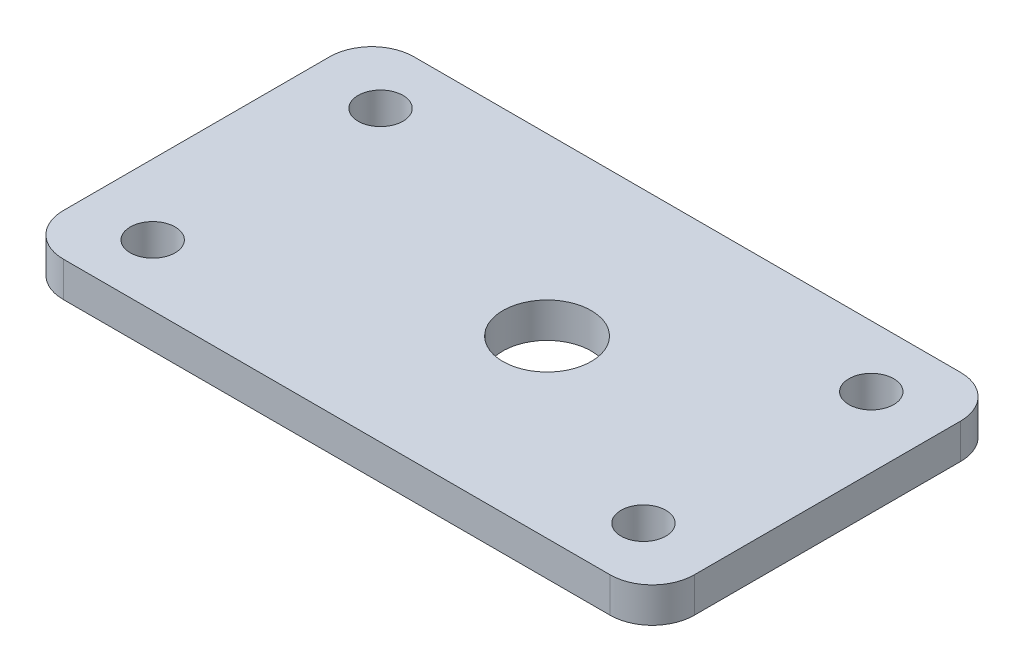
SolidWorks part; units mm, degrees
ref_plane "Front Plane" through (0, 0, 0) normal (0, 0, 1) x (1, 0, 0)
ref_plane "Top Plane" through (0, 0, 0) normal (0, 1, 0) x (1, 0, 0)
ref_plane "Right Plane" through (0, 0, 0) normal (1, 0, 0) x (0, 0, -1)
sketch "Sketch1" plane through (0, 0, 0) normal (0, 1, 0) x (1, 0, 0)
  line L0 (0, 0) -> (3.175, 0) construction
  line L1 (28.575, -15.875) -> (-28.575, -15.875)
  line L2 (28.575, -15.875) -> (28.575, 15.875)
  line L3 (28.575, 15.875) -> (-28.575, 15.875)
  line L4 (-28.575, -15.875) -> (-28.575, 15.875)
  line L5 (28.575, -15.875) -> (-28.575, 15.875) construction
  line L6 (28.575, 15.875) -> (-28.575, -15.875) construction
  circle A2 centre (3.175, 0) radius 4
  point P0 (0, 0)
  point P9 (-6.9555, 0)
  dimension "D3" = 8
  dimension "D4" = 31.75
  dimension "D1" = 57.15
  dimension "D2" = 31.75
extrude "Boss-Extrude1" add sketch "Sketch1" along normal blind 3.175 contours L3 L4 L1 L2 | A2
fillet "Fillet1" radius 3.81 4 edges at (28.575, 1.5875, -15.875) (28.575, 1.5875, 15.875) (-28.575, 1.5875, 15.875) (-28.575, 1.5875, -15.875)
sketch "Sketch2" plane through (0, 0, 0) normal (0, -1, 0) x (1, 0, 0)
  circle A0 centre (22.225, -10.3187) radius 2.032 construction
  circle A1 centre (22.225, 10.3188) radius 2.032 construction
  circle A2 centre (-22.225, -10.3188) radius 2.032 construction
  circle A3 centre (-22.225, 10.3187) radius 2.032 construction
  circle A4 centre (22.225, -10.3187) radius 2.032
  circle A5 centre (22.225, 10.3188) radius 2.032
  circle A6 centre (-22.225, -10.3188) radius 2.032
  circle A7 centre (-22.225, 10.3187) radius 2.032
extrude "Cut-Extrude1" cut sketch "Sketch2" against normal through all
